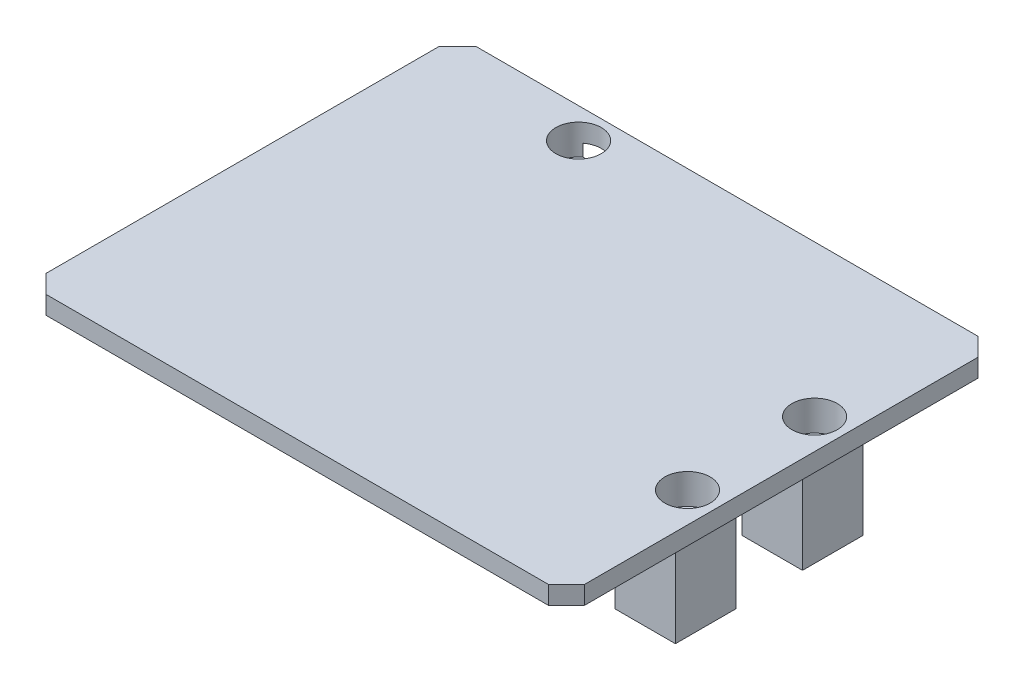
SolidWorks part; units mm, degrees
ref_plane "Front Plane" through (0, 0, 0) normal (0, 0, 1) x (1, 0, 0)
ref_plane "Top Plane" through (0, 0, 0) normal (0, 1, 0) x (1, 0, 0)
ref_plane "Right Plane" through (0, 0, 0) normal (1, 0, 0) x (0, 0, -1)
sketch "Sketch1" plane through (0, 0, 0) normal (0, 1, 0) x (1, 0, 0)
  line L0 (-44.5, 35.5) -> (44.5, 35.5)
  line L1 (-42.5, -33.5) -> (42.5, -33.5)
  line L2 (-42.5, -33.5) -> (-42.5, 33.5)
  line L3 (-42.5, 33.5) -> (42.5, 33.5)
  line L4 (42.5, -33.5) -> (42.5, 33.5)
  line L5 (-42.5, -33.5) -> (42.5, 33.5) construction
  line L6 (-42.5, 33.5) -> (42.5, -33.5) construction
  line L7 (44.5, -35.5) -> (44.5, 35.5)
  line L8 (-44.5, -35.5) -> (44.5, -35.5)
  line L9 (-44.5, -35.5) -> (-44.5, 35.5)
  circle A0 centre (-36.1567, 28.5) radius 2.1
  circle A1 centre (36.1567, 28.5) radius 2.1
  circle A3 centre (36.1567, -28.5) radius 2.1
  point P0 (0, 0)
  dimension "D4" = 4.2
  dimension "D1" = 85
  dimension "D2" = 67
  dimension "D5" = 5
  dimension "D3" = 2
extrude "Boss-Extrude1" add sketch "Sketch1" along normal blind 3 contours L1 L4 L3 L2 A3 A1 A0 | A1 | A3 | A0 region at (-0.0886, 0, 0.0698)
extrude "Boss-Extrude2" add sketch "Sketch1<3>" along normal blind 50 contours L9 L8 L7 L0 L4 L1 L2 L3 region at (0, 0, -34.3615)
sketch "Sketch1<3>" plane through (0, 0, 0) normal (0, 1, 0) x (1, 0, 0) same geometry as "Sketch1"
chamfer "Chamfer1" distance 3 angle 45 4 edges at (-44.5, 25, 35.5) (-44.5, 25, -35.5) (44.5, 25, -35.5) (44.5, 25, 35.5)
sketch "Sketch2" plane through (0, 3, 0) normal (0, 1, 0) x (1, 0, 0)
  line L0 (-42.5, 33.5) -> (42.5, 33.5) construction
  line L1 (-24.5, 33.5) -> (-14.5, 33.5)
  line L2 (-24.5, 33.5) -> (-24.5, 23.5)
  line L3 (-24.5, 23.5) -> (-14.5, 23.5)
  line L4 (-14.5, 33.5) -> (-14.5, 23.5)
  line L5 (42.5, -33.5) -> (42.5, 33.5) construction
  line L6 (42.5, 15.5) -> (32.5, 15.5)
  line L7 (42.5, 15.5) -> (42.5, 5.5)
  line L8 (42.5, 5.5) -> (32.5, 5.5)
  line L9 (32.5, 15.5) -> (32.5, 5.5)
  line L10 (42.5, -33.5) -> (42.5, 33.5) construction
  line L11 (42.5, -5.5) -> (32.5, -5.5)
  line L12 (42.5, -5.5) -> (42.5, -15.5)
  line L13 (42.5, -15.5) -> (32.5, -15.5)
  line L14 (32.5, -5.5) -> (32.5, -15.5)
  circle A0 centre (-19.5, 30.5) radius 2.1
  circle A1 centre (39.5, 10.5) radius 2.1
  circle A2 centre (39.5, -10.5) radius 2.1
  point P21 (32.5, 10.5)
  point P22 (32.5, -10.5)
  point P25 (-19.5, 23.5)
  dimension "D5" = 4.2
  dimension "D1" = 10
  dimension "D2" = 3
  dimension "D3" = 62
extrude "Boss-Extrude3" add sketch "Sketch2" along normal offset from surface (32 mm away) 15 up to face at (0, 50, 0)
extrude "Cut-Extrude1" cut sketch "Sketch1<4>" along normal through all from offset 3 contours L9 L8 L7 L0 L4 L1 L2 L3 region at (0, 0, -34.3615)
sketch "Sketch1<4>" plane through (0, 0, 0) normal (0, 1, 0) x (1, 0, 0) same geometry as "Sketch1"
extrude "Cut-Extrude2" cut sketch "Sketch2<2>" along normal through all from offset 15
sketch "Sketch2<2>" plane through (0, 3, 0) normal (0, 1, 0) x (1, 0, 0) same geometry as "Sketch2"
sketch "Sketch3" plane through (0, 0, 0) normal (0, -1, 0) x (1, 0, 0)
  circle A0 centre (-19.5, -30.5) radius 3.75
  circle A1 centre (39.5, -10.5) radius 3.75
  circle A2 centre (39.5, 10.5) radius 3.75
  dimension "D1" = 7.5
extrude "Cut-Extrude3" cut sketch "Sketch3" against normal blind 5
mirror "Mirror5" about plane through (0, 18, 0) normal (0, 1, 0) of bodies 106
sketch "Sketch4" plane through (0, 33, 0) normal (0, -1, 0) x (1, 0, 0)
  line L1 (-52.9353, 43.2416) -> (49.609, 43.2416)
  line L2 (-52.9353, 43.2416) -> (-52.9353, -39.117)
  line L3 (-52.9353, -39.117) -> (49.609, -39.117)
  line L4 (49.609, 43.2416) -> (49.609, -39.117)
  line L5 (-52.9353, 43.2416) -> (49.609, -39.117) construction
  line L6 (-52.9353, -39.117) -> (49.609, 43.2416) construction
  point P0 (-1.6631, 2.0623)
extrude "Cut-Extrude4" cut sketch "Sketch4" along normal blind 40 from offset 15
